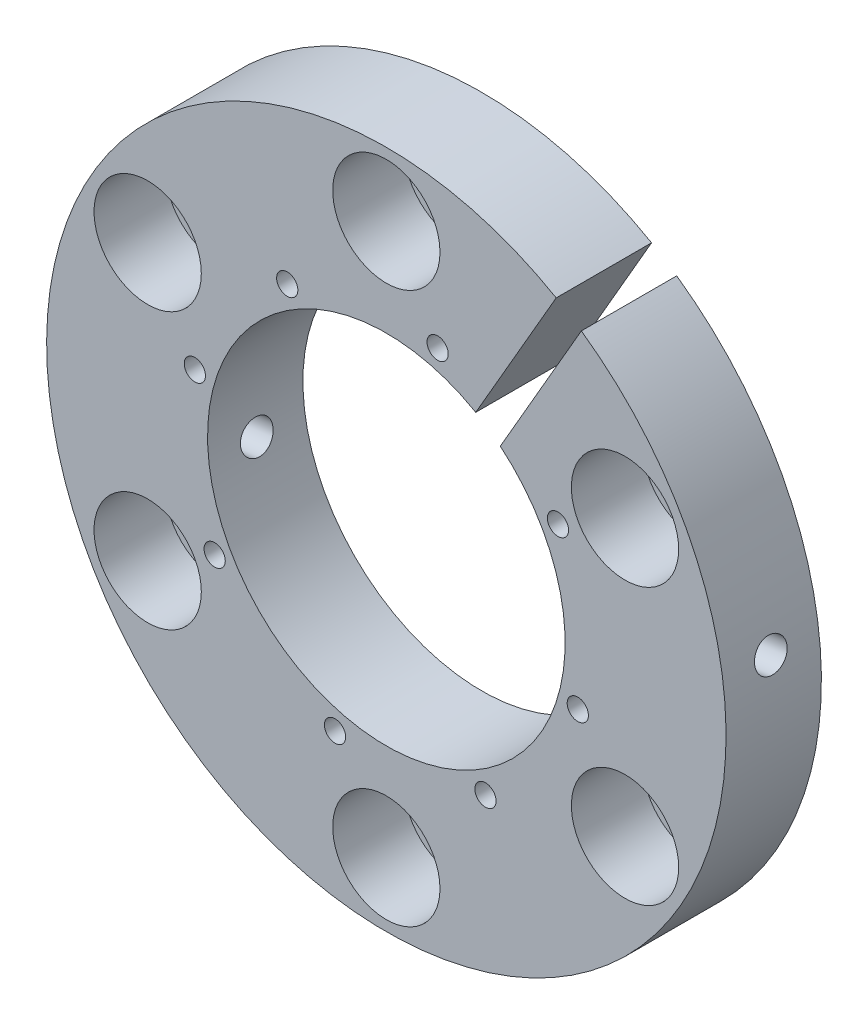
SolidWorks part; units mm, degrees
ref_plane "Front" through (0, 0, 0) normal (0, 0, 1) x (1, 0, 0)
ref_plane "Top" through (0, 0, 0) normal (0, 1, 0) x (1, 0, 0)
ref_plane "Right" through (0, 0, 0) normal (1, 0, 0) x (0, 0, -1)
sketch "Sketch2" plane through (0, 0, 0) normal (0, 0, 1) x (1, 0, 0)
  circle A0 centre (0, 0) radius 36.195
  dimension "D1" = 72.39
extrude "Boss-Extrude1" add sketch "Sketch2" along normal blind 10.16
sketch "Sketch3" plane through (0, 0, 10.16) normal (0, 0, 1) x (1, 0, 0)
  circle A0 centre (0, 0) radius 19.05
  dimension "D1" = 38.1
extrude "Cut-Extrude1" cut sketch "Sketch3" against normal through all
sketch "Sketch17" plane through (0, 0, 10.16) normal (0, 0, 1) x (1, 0, 0)
  circle A0 centre (0, 0) radius 29.3624
  dimension "D1" = 58.7248
hole_wizard "CBORE for 1/4 Hex Head Bolt1" positions "Sketch19" profile "Sketch18" counterbore size "1/4" standard "ANSI Inch" end condition through all
sketch "Sketch19" plane through (0, 0, 10.16) normal (0, 0, 1) x (1, 0, 0)
  circle A0 centre (0, 0) radius 29.3624 construction
  point P0 (0, 29.3624)
sketch "Sketch18" plane through (0, 29.3624, 10.16) normal (1, 0, 0) x (0, -1, 0)
  line L0 (0, 0) -> (0, 10.16)
  line L1 (0, 10.16) -> (3.3782, 10.16)
  line L3 (3.3782, 10.16) -> (3.3782, 7.62)
  line L4 (3.3782, 7.62) -> (5.715, 7.62)
  line L5 (5.715, 7.62) -> (5.715, 0)
  line L7 (5.715, 0) -> (0, 0)
  line L11 (0, -6.35) -> (0, 107.95) construction
  dimension "Thru Hole Dia." = 6.7564
  dimension "Thru Hole Depth" = 10.16
  dimension "C'Bore Dia." = 11.43
  dimension "C'Bore Depth" = 7.62
pattern_circular "CirPattern1" count 6 over 360 about axis through (0, 0, 0) along (0, 0, 1) of "CBORE for 1/4 Hex Head Bolt1" reverse direction yes
ref_axis "Axis1" through (0, 0, 0) along (0, 0, 1)
sketch "Sketch22" plane through (0, 0, 10.16) normal (0, 0, 1) x (1, 0, 0)
  circle A0 centre (0, 0) radius 21.209
  dimension "D1" = 42.418
sketch "Sketch28" plane through (0, 0, 10.16) normal (0, 0, 1) x (1, 0, 0)
  line L0 (0, 0) -> (0, 42.8888) construction
  line L1 (0, 0) -> (-23.2342, 40.2428) construction
  line L2 (0, 0) -> (10.932, 40.7986) construction
  line L3 (0, 0) -> (22.4962, 38.9646) construction
  dimension "D1" = 30
  dimension "D2" = 45
  dimension "D3" = 30
hole_wizard "#4-40 Tapped Hole1" positions "Sketch37" profile "Sketch35" tap size "#4-40" standard "ANSI Inch"
sketch "Sketch37" plane through (0, 0, 10.16) normal (0, 0, 1) x (1, 0, 0)
  line L0 (0, 0) -> (10.932, 40.7986) construction
  point P0 (5.466, 20.3993)
sketch "Sketch35" plane through (5.466, 20.3993, 10.16) normal (1, 0, 0) x (0, -1, 0)
  line L0 (0, 0) -> (0, 8.2992)
  line L1 (0, 8.2992) -> (1.1303, 7.62)
  line L2 (1.1303, 7.62) -> (1.1303, 0)
  line L5 (1.1303, 0) -> (0, 0)
  line L10 (0, 8.2992) -> (-1.1303, 7.62) construction
  line L11 (0, -6.35) -> (0, 107.95) construction
  dimension "Tap Drill Dia." = 2.2606
  dimension "Tap Drill Depth" = 7.62
  dimension "Drill Angle" = 118
cosmetic thread "Hole Thread6" parameters "D1"=5.588, "D2"=2.8448
pattern_circular "CirPattern5" count 8 over 360 about axis through (0, 0, 0) along (0, 0, 1) of "#4-40 Tapped Hole1"
sketch "Sketch44" plane through (0, 0, 10.16) normal (0, 0, 1) x (1, 0, 0)
  line L0 (0, 0) -> (22.4962, 38.9646)
  line L1 (22.4962, 38.9646) -> (25.2459, 37.3771)
  line L2 (25.2459, 37.3771) -> (2.7496, -1.5875)
  line L3 (2.7496, -1.5875) -> (0, 0)
  dimension "D1" = 3.175
extrude "Cut-Extrude9" cut sketch "Sketch44" against normal through all
sketch "Sketch46" plane through (0, 0, 10.16) normal (0, 0, 1) x (1, 0, 0)
  line L0 (0, 0) -> (-20.3993, 5.466) construction
  line L1 (0, 0) -> (-42.1077, -5.5436) construction
  dimension "D1" = 22.5
sketch "Sketch47" plane through (0, 0, 0) normal (0, 0, -1) x (-1, 0, 0)
  line L0 (0, 0) -> (42.1077, -5.5436) construction
hole_wizard "#8-32 Tapped Hole3" positions "3DSketch6" profile "Sketch50" tap size "#8-32" standard "ANSI Inch" end condition through all
sketch3d "3DSketch6"
  line L0 (0, 0, 0) -> (-42.1077, -5.5436, 0) construction
  line L1 (0, 0, 10.16) -> (-42.1077, -5.5436, 10.16) construction
  point P0 (-35.8853, -4.7244, 5.08)
  dimension "D1" = 5.08
  dimension "D2" = 5.08
sketch "Sketch50" plane through (-35.8853, -4.7244, 5.08) normal (0, 0, 1) x (0.1305, -0.9914, 0)
  line L0 (0, 0) -> (0, 76.8047)
  line L1 (0, 76.8047) -> (1.7272, 76.8047)
  line L2 (1.7272, 76.8047) -> (1.7272, 0)
  line L5 (1.7272, 0) -> (0, 0)
  line L11 (0, -6.35) -> (0, 107.95) construction
  dimension "Thru Tap Drill Dia." = 3.4544
  dimension "Thru Tap Drill Depth" = 76.8047
cosmetic thread "Hole Thread8" parameters "D2"=4.1656
